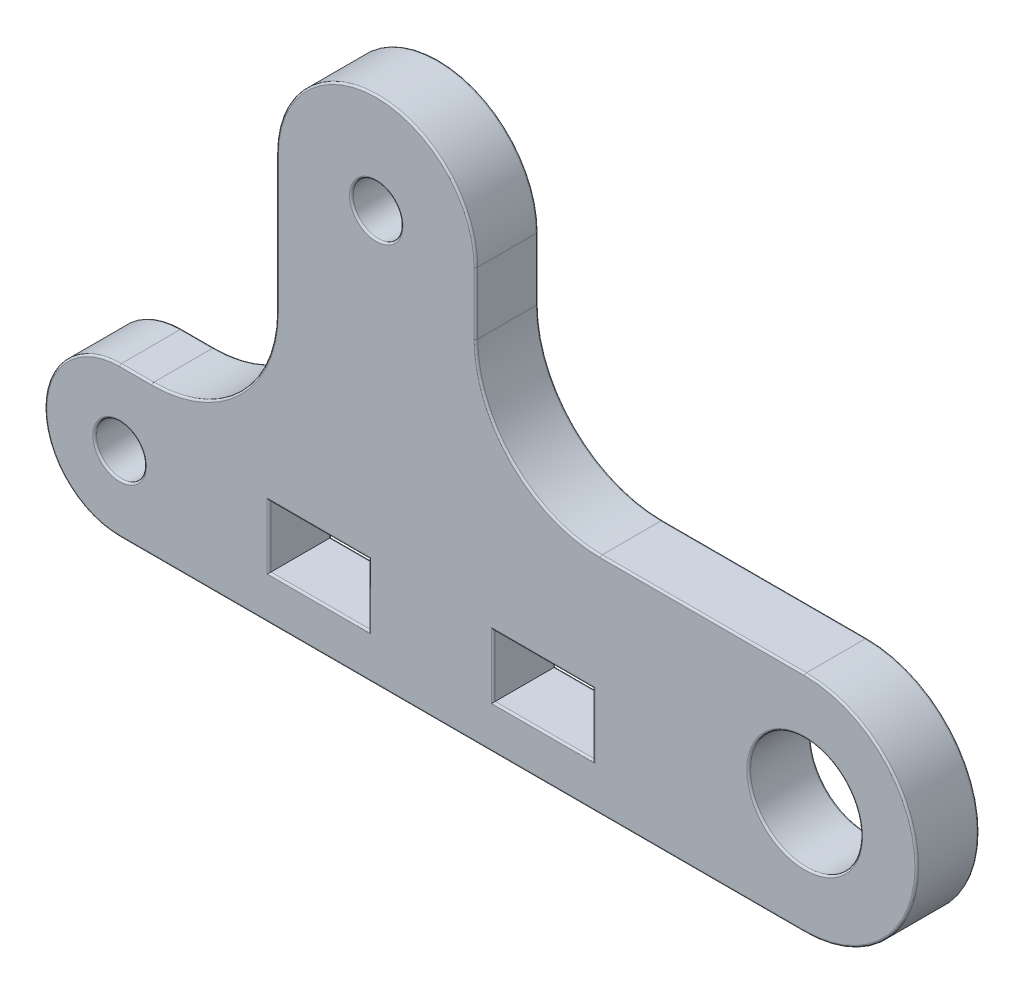
SolidWorks part; units mm, degrees
ref_plane "Płaszczyzna przednia" through (0, 0, 0) normal (0, 0, 1) x (1, 0, 0)
ref_plane "Płaszczyzna górna" through (0, 0, 0) normal (0, 1, 0) x (1, 0, 0)
ref_plane "Płaszczyzna prawa" through (0, 0, 0) normal (1, 0, 0) x (0, 0, -1)
sketch "Szkic1" plane through (0, 0, 0) normal (0, 0, 1) x (1, 0, 0)
  line L0 (-27.5, 0) -> (27.5, 0)
  line L1 (-27.5, 12) -> (-24.9, 12)
  line L2 (-14.9, 22) -> (-14.9, 33)
  line L3 (1.1, 33) -> (1.1, 28)
  line L4 (11.1, 18) -> (27.5, 18)
  line L5 (-27.5, 6) -> (-15.5, 6) construction
  line L7 (-15.5, 3.5) -> (-7.5, 3.5)
  line L8 (-15.5, 3.5) -> (-15.5, 8.5)
  line L9 (-15.5, 8.5) -> (-7.5, 8.5)
  line L10 (-7.5, 3.5) -> (-7.5, 8.5)
  line L15 (2.5, 3.5) -> (10.5, 3.5)
  line L16 (2.5, 3.5) -> (2.5, 8.5)
  line L17 (2.5, 8.5) -> (10.5, 8.5)
  line L18 (10.5, 3.5) -> (10.5, 8.5)
  arc A0 (-27.5, 0) -> (-27.5, 12) centre (-27.5, 6) cw
  arc A1 (27.5, 0) -> (27.5, 18) centre (27.5, 9) ccw
  circle A2 centre (-27.5, 6) radius 2
  circle A3 centre (27.5, 9) radius 4.5
  circle A4 centre (-6.9, 33) radius 2
  circle A5 centre (-6.9, 33) radius 8 construction
  arc A6 (-14.9, 33) -> (1.1, 33) centre (-6.9, 33) cw
  arc A7 (-14.9, 22) -> (-24.9, 12) centre (-24.9, 22) cw
  arc A8 (11.1, 18) -> (1.1, 28) centre (11.1, 28) cw
  dimension "D2" = 6
  dimension "D3" = 9
  dimension "D4" = 4
  dimension "D5" = 9
  dimension "D6" = 33
  dimension "D8" = 16
  dimension "D9" = 10
  dimension "D10" = 10
  dimension "D1" = 55
  dimension "D7" = 6.9
  dimension "D11" = 12
  dimension "D12" = 8
  dimension "D13" = 5
  dimension "D14" = 10
extrude "Dodanie-wyciągnięcie1" add sketch "Szkic1" along normal mid plane 5
fillet "Zaokrąglenie1" radius 0.15 42 edges at (10.5, 6, -2.5) (6.5, 3.5, -2.5) (2.5, 6, -2.5) (6.5, 8.5, -2.5) (-7.5, 6, -2.5) (-11.5, 3.5, -2.5) (-15.5, 6, -2.5) (-11.5, 8.5, -2.5) (-4.9, 33, -2.5) (32, 9, -2.5) (0, 0, -2.5) (36.5, 9, -2.5) (19.3, 18, -2.5) (4.0289, 20.9289, -2.5) (1.1, 30.5, -2.5) (-6.9, 41, -2.5) (-14.9, 27.5, -2.5) (-17.8289, 14.9289, -2.5) (-26.2, 12, -2.5) (-33.5, 6, -2.5) (-25.5, 6, -2.5) (6.5, 3.5, 2.5) (10.5, 6, 2.5) (6.5, 8.5, 2.5) (2.5, 6, 2.5) (-4.9, 33, 2.5) (-25.5, 6, 2.5) (32, 9, 2.5) (-26.2, 12, 2.5) (-17.8289, 14.9289, 2.5) (-14.9, 27.5, 2.5) (-6.9, 41, 2.5) (1.1, 30.5, 2.5) (4.0289, 20.9289, 2.5) (19.3, 18, 2.5) (36.5, 9, 2.5) (0, 0, 2.5) (-33.5, 6, 2.5) (-11.5, 3.5, 2.5) (-7.5, 6, 2.5) (-11.5, 8.5, 2.5) (-15.5, 6, 2.5)
